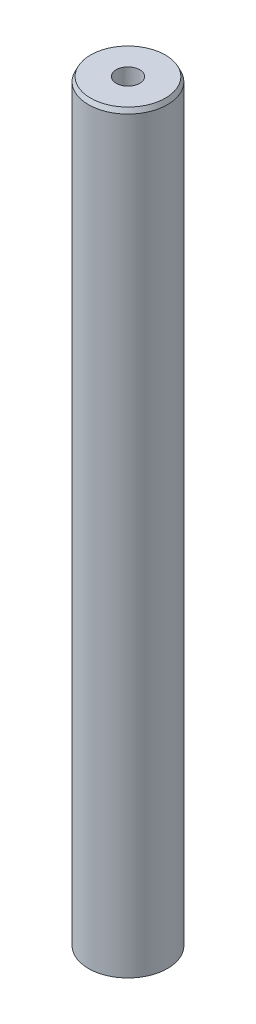
SolidWorks part; units mm, degrees
ref_plane "Front Plane" through (0, 0, 0) normal (0, 0, 1) x (1, 0, 0)
ref_plane "Top Plane" through (0, 0, 0) normal (0, 1, 0) x (1, 0, 0)
ref_plane "Right Plane" through (0, 0, 0) normal (1, 0, 0) x (0, 0, -1)
sketch "Sketch1" plane through (0, 0, 0) normal (0, 1, 0) x (1, 0, 0)
  circle A0 centre (0, 0) radius 12.5
  dimension "SHAFT_OD" = 25
extrude "Boss-Extrude1" add sketch "Sketch1" along normal blind 238.592
sketch "Sketch2" plane through (0, 0, 0) normal (0, 1, 0) x (1, 0, 0)
  circle A0 centre (0, 0) radius 3.7266
  dimension "BORE_D" = 7.4532
extrude "Cut-Extrude1" cut sketch "Sketch2" along normal through all
chamfer "Chamfer1" distance 1.4453 angle 25.112 2 edges at (0, 238.592, 12.5) (0, 0, 12.5) first distance on face at (0, 238.592, 12.5) first distance on face at (0, 0, 3.7266)
